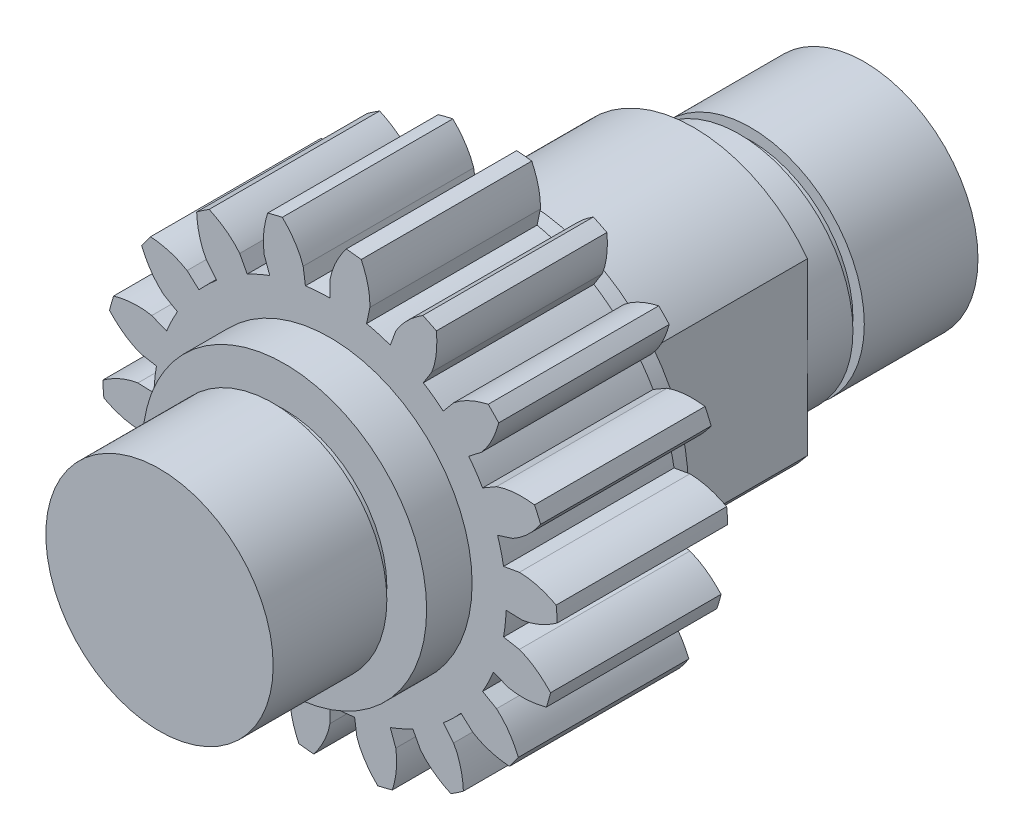
SolidWorks part; units mm, degrees
ref_plane "Front Plane" through (0, 0, 0) normal (0, 0, 1) x (1, 0, 0)
ref_plane "Top Plane" through (0, 0, 0) normal (0, 1, 0) x (1, 0, 0)
ref_plane "Right Plane" through (0, 0, 0) normal (1, 0, 0) x (0, 0, -1)
sketch "Sketch1" plane through (0, 0, 0) normal (0, 0, 1) x (1, 0, 0)
  line L0 (0, 16.9125) -> (6.1737, 15.7454) construction
  line L1 (6.1737, 15.7454) -> (11.4953, 12.4053) construction
  line L2 (11.4953, 12.4053) -> (15.2304, 7.3531) construction
  line L3 (15.2304, 7.3531) -> (16.8635, 1.286) construction
  line L4 (6.1737, 15.7454) -> (0.3242, 18.0389) construction
  line L5 (11.4953, 12.4053) -> (2.2781, 20.9463) construction
  line L6 (15.2304, 7.3531) -> (7.0354, 24.3274) construction
  line L7 (16.8635, 1.286) -> (14.9469, 26.418)
  line L8 (0.308, 17.9974) -> (3.4324, 17.6697) construction
  line L9 (1.8702, 17.8335) -> (0, 0) construction
  line L10 (0, 16.9125) -> (0.0099, 0.0943)
  line L11 (0.0099, 0.0943) -> (3.5086, 16.5445)
  circle A0 centre (0, 0) radius 15.5
  circle A1 centre (0, 0) radius 20
  circle A2 centre (0, 0) radius 16.9125 construction
  circle A3 centre (0, 0) radius 18 construction
  spline S0 degree 3 poles (0, 16.9125) (0.2837, 18.4617) (3.9181, 23.8314) (10.3777, 25.9859) (14.9469, 26.418) knots 0 0 0 0 0.250077 1 1 1 1
  spline S1 degree 3 poles (3.5086, 16.5445) (3.5525, 18.1189) (1.1112, 24.1257) (-4.7609, 27.5735) (-9.1411, 28.9442) knots 0 0 0 0 0.250077 1 1 1 1
  dimension "D1" = 40
  dimension "D2" = 36
  dimension "D3" = 33.825
  dimension "D4" = 31
  dimension "D5" = 6.283
  dimension "D6" = 6.283
  dimension "D7" = 12.566
  dimension "D8" = 18.849
  dimension "D9" = 25.132
  dimension "D10" = 3.1415
extrude "Boss-Extrude1" add sketch "Sketch1" along normal blind 15 contours L10 A0 L11 | L11 A0 L10 | L11 S1 A1 S0 L10 A0 region at (1.8236, 17.3894, 0) region at (-0.0369, -0.3516, 0) region at (1.0791, 10.2897, 0)
pattern_circular "CirPattern1" count 18 over 360 about axis through (0, 0, 15) along (0, 0, 1) of "Boss-Extrude1"
sketch "Sketch3" plane through (0, 0, 15) normal (0, 0, 1) x (1, 0, 0)
  circle A0 centre (0, 0) radius 12.5
  circle A1 centre (0, 0) radius 10
  dimension "D1" = 25
  dimension "D2" = 20
extrude "Boss-Extrude2" add sketch "Sketch3" along normal blind 4 contours A0
extrude "Boss-Extrude3" add sketch "Sketch3<3>" along normal blind 15 contours A1
sketch "Sketch3<3>" plane through (0, 0, 15) normal (0, 0, 1) x (1, 0, 0) same geometry as "Sketch3"
sketch "Sketch4" plane through (0, 0, 0) normal (1, 0, 0) x (0, 0, -1)
  line L0 (0, 0) -> (5.8047, 0) construction
  line L1 (-19, 10) -> (-20, 10)
  line L2 (-19, 10) -> (-19, 9)
  line L3 (-19, 9) -> (-20, 9)
  line L4 (-20, 10) -> (-20, 9)
  point P8 (-19.5, 9)
  dimension "D1" = 1
  dimension "D2" = 18
revolve "Cut-Revolve1" cut sketch "Sketch4" angle 360 about L0
sketch "Sketch5" plane through (0, 0, 0) normal (0, 0, -1) x (-1, 0, 0)
  circle A0 centre (0, 0) radius 12.5
  circle A1 centre (0, 0) radius 10
  circle A2 centre (0, 0) radius 14.5
  dimension "D1" = 20
  dimension "D2" = 25
  dimension "D3" = 29
extrude "Boss-Extrude4" add sketch "Sketch5" along normal blind 2 contours A2
extrude "Boss-Extrude5" add sketch "Sketch5<3>" along normal blind 17 contours A0
sketch "Sketch5<3>" plane through (0, 0, 0) normal (0, 0, -1) x (-1, 0, 0) same geometry as "Sketch5"
extrude "Boss-Extrude6" add sketch "Sketch5<4>" along normal blind 32 contours A1
sketch "Sketch5<4>" plane through (0, 0, 0) normal (0, 0, -1) x (-1, 0, 0) same geometry as "Sketch5"
sketch "Sketch6" plane through (0, 0, 0) normal (1, 0, 0) x (0, 0, -1)
  line L0 (32, 10) -> (17, 10) construction
  line L1 (22, 10) -> (21, 10)
  line L2 (22, 10) -> (22, 9)
  line L3 (22, 9) -> (21, 9)
  line L4 (21, 10) -> (21, 9)
  line L5 (32, -10) -> (32, 10) construction
  line L6 (0, 0) -> (43.7071, 0) construction
  dimension "D1" = 1
  dimension "D2" = 10
  dimension "D3" = 18
revolve "Cut-Revolve2" cut sketch "Sketch6" angle 360 about L6
sketch "Sketch7" plane through (0, 0, -17) normal (0, 0, -1) x (-1, 0, 0)
  line L0 (0, 0) -> (0, -6.2578) construction
  line L1 (-10, 7.5) -> (-10, -7.5)
  line L2 (10, 7.5) -> (10, -7.5)
  circle A0 centre (0, 0) radius 12.5 construction
  arc A1 (-10, -7.5) -> (10, -7.5) centre (0, 0) ccw
  arc A2 (10, 7.5) -> (-10, 7.5) centre (0, 0) ccw
  dimension "D1" = 10
extrude "Cut-Extrude1" cut sketch "Sketch7" against normal up to surface (15 mm away) flip side to cut up to face at (-12.5, 0, -2)
